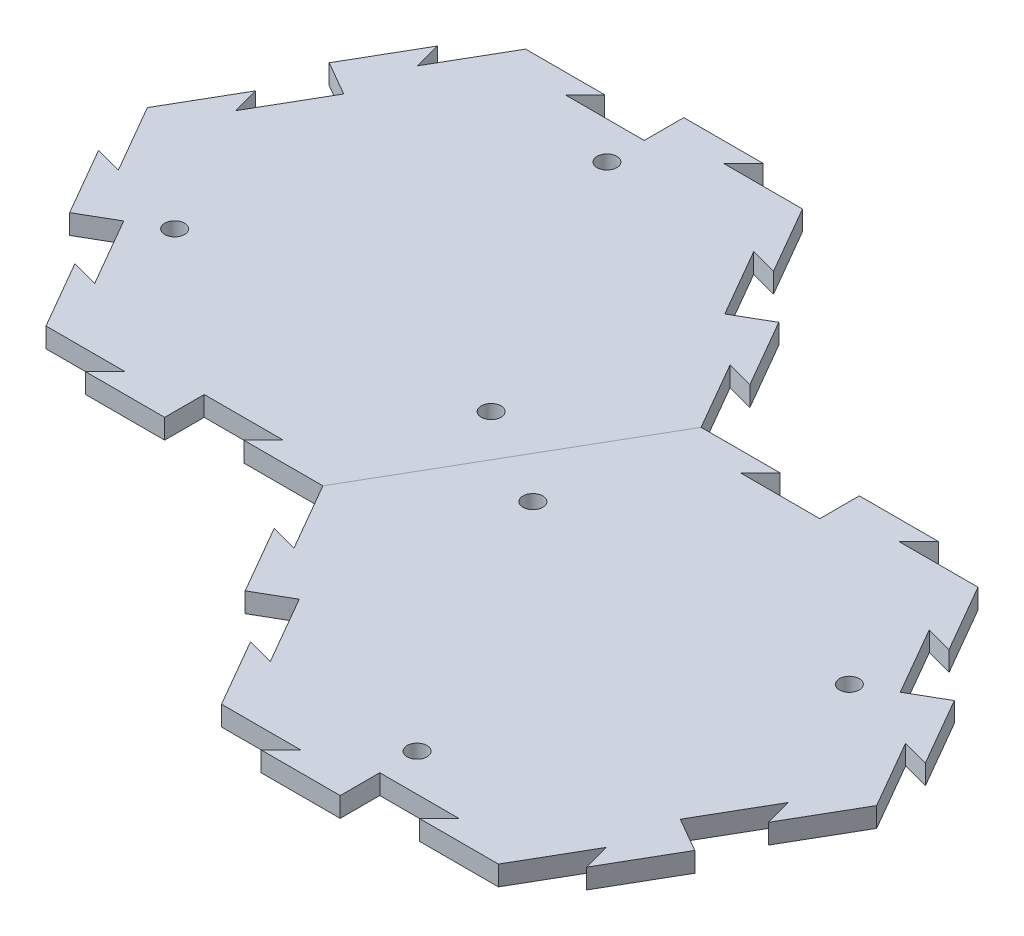
SolidWorks part; units mm, degrees
material "Cedar"
ref_plane "Front Plane" through (0, 0, 0) normal (0, 0, 1) x (1, 0, 0)
ref_plane "Top Plane" through (0, 0, 0) normal (0, 1, 0) x (1, 0, 0)
ref_plane "Right Plane" through (0, 0, 0) normal (1, 0, 0) x (0, 0, -1)
sketch "Sketch1" plane through (0, 0, 0) normal (0, 1, 0) x (1, 0, 0)
  line L0 (0, 0) -> (88.9, 0) construction
  line L1 (88.9, 0) -> (44.45, 76.9897)
  line L2 (44.45, 76.9897) -> (-44.45, 76.9897)
  line L3 (-44.45, 76.9897) -> (-88.9, 0)
  line L4 (-88.9, 0) -> (-44.45, -76.9897)
  line L5 (-44.45, -76.9897) -> (44.45, -76.9897)
  line L6 (44.45, -76.9897) -> (88.9, 0)
  circle A0 centre (0, 0) radius 76.9897 construction
  dimension "D1" = 88.9
extrude "Boss-Extrude1" add sketch "Sketch1" against normal blind 6.35
sketch "Sketch2" plane through (0, 0, 0) normal (0, 1, 0) x (1, 0, 0)
  point P1 (0, 0)
ref_axis "Axis1" through (0, 0, 0) along (0, 1, 0)
sketch "Sketch9" plane through (0, 0, 0) normal (0, 1, 0) x (1, 0, 0)
  line L1 (50.8, -29.3294) -> (0, 58.6588) construction
  line L2 (0, 58.6588) -> (-50.8, -29.3294) construction
  line L3 (-50.8, -29.3294) -> (50.8, -29.3294) construction
  circle A0 centre (0, 0) radius 29.3294 construction
  circle A1 centre (-50.8, -29.3294) radius 3.175
  dimension "D2" = 6.35
  dimension "D1" = 101.6
extrude "Cut-Extrude3" cut sketch "Sketch9" against normal through all
pattern_circular "CirPattern6" count 3 over 360 about axis through (0, 0, 0) along (0, 1, 0) of "Cut-Extrude3"
mirror "Mirror3" about plane through (44.45, -6.35, 76.9897) normal (0.866, 0, 0.5) of bodies 121 125
sketch "Sketch10" plane through (0, 0, 0) normal (0, 1, 0) x (1, 0, 0)
  line L0 (44.45, 76.9897) -> (57.15, 54.9926) construction
  line L1 (57.15, 54.9926) -> (48.4757, 57.3169)
  line L2 (48.4757, 57.3169) -> (61.1757, 35.3198)
  line L3 (61.1757, 35.3198) -> (66.675, 38.4948)
  line L4 (57.15, 54.9926) -> (66.675, 38.4948)
  line L5 (88.9, 0) -> (44.45, 76.9897) construction
  dimension "D1" = 45
  dimension "D2" = 6.35
extrude "Cut-Extrude4" cut sketch "Sketch10" against normal through all
sketch "Sketch11" plane through (0, 0, 0) normal (0, 1, 0) x (1, 0, 0)
  line L0 (66.675, 38.4948) -> (88.9, 0) construction
  line L1 (66.675, 38.4948) -> (72.1743, 41.6698)
  line L2 (72.1743, 41.6698) -> (84.8743, 19.6728)
  line L3 (84.8743, 19.6728) -> (76.2, 21.997)
  line L4 (76.2, 21.997) -> (66.675, 38.4948)
  line L5 (76.2, 21.997) -> (88.9, 0) construction
  line L6 (76.2, 21.997) -> (88.9, 0) construction
  line L7 (88.9, 0) -> (66.675, 38.4948) construction
  line L8 (44.45, -76.9897) -> (88.9, 0) construction
  dimension "D1" = 45
  dimension "D2" = 6.35
extrude "Boss-Extrude4" add sketch "Sketch11" against normal blind 6.35
pattern_circular "CirPattern7" count 6 over 360 about axis through (0, 0, 0) along (0, 1, 0) skipping 5 of "Cut-Extrude4", "Boss-Extrude4"
sketch "Sketch12" plane through (0, 0, 0) normal (0, 1, 0) x (1, 0, 0)
  line L0 (177.8, 0) -> (88.9, -153.9793) construction
  point P4 (133.35, -76.9897)
ref_axis "Axis2" through (133.35, 0, 76.9897) along (0, 1, 0)
sketch "Sketch13" plane through (0, 0, 0) normal (0, 1, 0) x (1, 0, 0)
  line L0 (177.8, 0) -> (190.5, -21.997) construction
  line L1 (190.5, -21.997) -> (181.8257, -19.6728)
  line L2 (181.8257, -19.6728) -> (194.5257, -41.6698)
  line L3 (194.5257, -41.6698) -> (200.025, -38.4948)
  line L4 (190.5, -21.997) -> (200.025, -38.4948)
  line L5 (177.8, 0) -> (222.25, -76.9897) construction
  point P5 (177.8, 0)
  point P7 (0, 0)
  dimension "D1" = 45
  dimension "D2" = 6.35
extrude "Cut-Extrude5" cut sketch "Sketch13" against normal through all
sketch "Sketch14" plane through (0, 0, 0) normal (0, 1, 0) x (1, 0, 0)
  line L0 (200.025, -38.4948) -> (222.25, -76.9897) construction
  line L1 (200.025, -38.4948) -> (205.5243, -35.3198)
  line L2 (205.5243, -35.3198) -> (218.2243, -57.3169)
  line L3 (218.2243, -57.3169) -> (209.55, -54.9926)
  line L4 (209.55, -54.9926) -> (200.025, -38.4948)
  line L5 (209.55, -54.9926) -> (222.25, -76.9897) construction
  line L6 (209.55, -54.9926) -> (222.25, -76.9897) construction
  point P5 (222.25, -76.9897)
  point P7 (200.025, -38.4948)
  dimension "D1" = 45
  dimension "D2" = 6.35
extrude "Boss-Extrude5" add sketch "Sketch14" against normal blind 6.35
pattern_circular "CirPattern8" count 6 over 360 about axis through (133.35, 0, 76.9897) along (0, 1, 0) skipping 2 of "Cut-Extrude5", "Boss-Extrude5"
